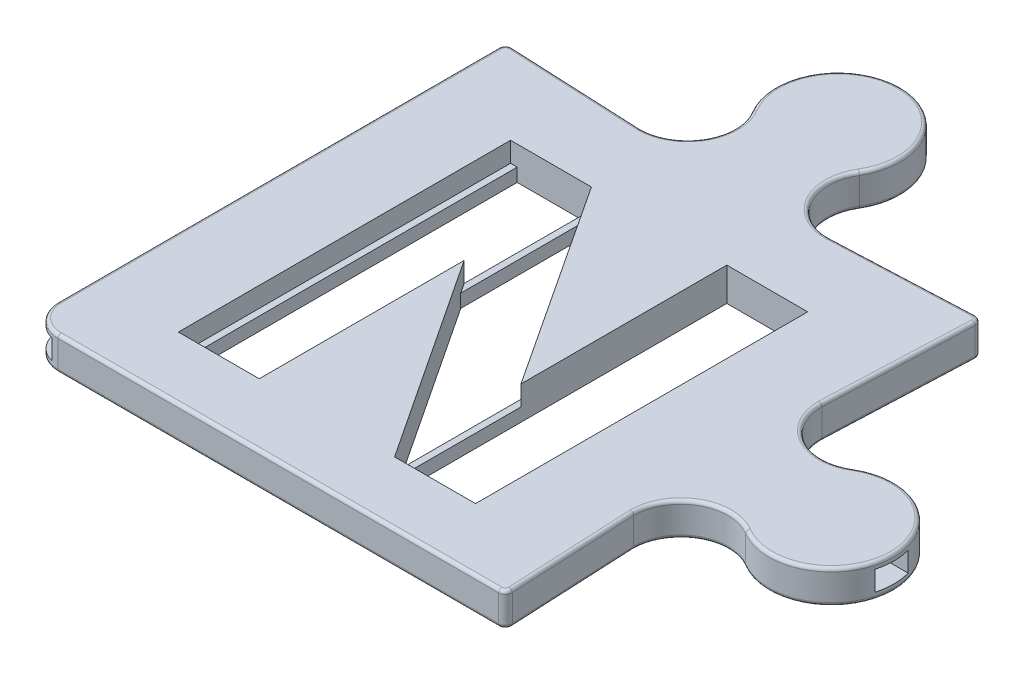
SolidWorks part; units mm, degrees
ref_plane "Front Plane" through (0, 0, 0) normal (0, 0, 1) x (1, 0, 0)
ref_plane "Top Plane" through (0, 0, 0) normal (0, 1, 0) x (1, 0, 0)
ref_plane "Right Plane" through (0, 0, 0) normal (1, 0, 0) x (0, 0, -1)
sketch "Sketch1" plane through (0, 0, 0) normal (0, 1, 0) x (1, 0, 0)
  line L0 (-31, -36) -> (37, -36) construction
  line L1 (-36, 37) -> (-36, -31) construction
  line L2 (-14.1421, 36) -> (-36, 37) construction
  line L3 (37, 37) -> (14.1421, 36) construction
  line L4 (36, 13.1421) -> (37, 37) construction
  line L5 (37, -36) -> (36, -15.1421) construction
  line L6 (-35.4, 36.3719) -> (-35.4, -31)
  line L7 (-36, 36) -> (36, 36) construction
  line L8 (-36, 36) -> (-36, -36) construction
  line L9 (-36, -36) -> (36, -36) construction
  line L10 (36, 36) -> (36, -36) construction
  line L11 (-31, -35.4) -> (36.3705, -35.4)
  line L12 (36.3705, -35.4) -> (35.4, -15.1568)
  line L13 (35.4, 13.155) -> (36.3732, 36.372)
  line L14 (36.3732, 36.372) -> (14.1555, 35.4)
  line L15 (-14.1562, 35.4) -> (-35.4, 36.3719)
  line L16 (-30, -24) -> (30, -24) construction
  line L17 (-30, 29) -> (30, 29) construction
  line L18 (-30, 29) -> (-30, -31) construction
  line L19 (-30, -31) -> (30, -31) construction
  line L20 (30, 29) -> (30, -31) construction
  line L21 (-30, 24) -> (30, 24) construction
  line L22 (-30, 24) -> (-30, -26) construction
  line L23 (-30, -26) -> (30, -26) construction
  line L24 (30, 24) -> (30, -26) construction
  arc A0 (-36, -31) -> (-31, -36) centre (-31, -31) ccw construction
  arc A1 (-14.1421, 36) -> (-8.571, 45.8485) centre (-14.1421, 42.5) ccw construction
  arc A2 (8.571, 45.8485) -> (-8.571, 45.8485) centre (0, 51) ccw construction
  arc A3 (8.571, 45.8485) -> (14.1421, 36) centre (14.1421, 42.5) ccw construction
  arc A4 (36, 13.1421) -> (45.8485, 7.571) centre (42.5, 13.1421) ccw construction
  arc A5 (45.8485, -9.571) -> (45.8485, 7.571) centre (51, -1) ccw construction
  arc A6 (45.8485, -9.571) -> (36, -15.1421) centre (42.5, -15.1421) ccw construction
  arc A7 (-35.4, -31) -> (-31, -35.4) centre (-31, -31) ccw
  arc A8 (46.1576, -9.0567) -> (35.4, -15.1568) centre (42.5, -15.1421) ccw
  arc A9 (46.1576, -9.0567) -> (46.1576, 7.0567) centre (51, -1) ccw
  arc A10 (35.4, 13.155) -> (46.1576, 7.0567) centre (42.5, 13.1421) ccw
  arc A11 (8.0567, 46.1576) -> (14.1555, 35.4) centre (14.1421, 42.5) ccw
  arc A12 (8.0567, 46.1576) -> (-8.0567, 46.1576) centre (0, 51) ccw
  arc A13 (-14.1562, 35.4) -> (-8.0567, 46.1576) centre (-14.1421, 42.5) ccw
  point P32 (36, 0)
  point P34 (0, 36)
  dimension "D5" = 6.5
  dimension "D6" = 10
  dimension "D7" = 6.5
  dimension "D13" = 5
  dimension "D9" = 10
  dimension "D11" = 6.5
  dimension "D12" = 6.5
  dimension "D1" = 72
  dimension "D2" = 1
  dimension "D3" = 1
  dimension "D4" = 15
  dimension "D8" = 1
  dimension "D10" = 35
  dimension "D14" = 15
  dimension "D15" = 36
  dimension "D16" = 1
  dimension "D18" = 60
  dimension "D19" = 60
  dimension "D20" = 5
  dimension "D21" = 6
  dimension "D22" = 5
  dimension "D23" = 50
  dimension "D24" = 2
  dimension "D17" = 0.6
extrude "Boss-Extrude1" add sketch "Sketch1" along normal blind 5
sketch "Sketch6" plane through (0, 0, 0) normal (0, -1, 0) x (1, 0, 0)
  line L0 (-35.4, -36.3719) -> (-35.4, 31) construction
  line L1 (-35.4, 18.4) -> (-27.4, 18.4)
  line L2 (-35.4, 18.4) -> (-35.4, -15.6)
  line L3 (-35.4, -15.6) -> (-27.4, -15.6)
  line L4 (-27.4, 18.4) -> (-27.4, -15.6)
  line L5 (-31, 35.4) -> (36.3705, 35.4) construction
  line L6 (-35.4, 15.15) -> (-30.4, 15.15)
  line L7 (-35.4, 15.15) -> (-35.4, -12.35)
  line L8 (-35.4, -12.35) -> (-30.4, -12.35)
  line L9 (-30.4, 15.15) -> (-30.4, -12.35)
  point P15 (-27.4, 1.4)
  point P16 (-30.4, 1.4)
  line M28 (-35.4, 31) -> (-35.4, -36.3719)
  dimension "D1" = 8
  dimension "D2" = 20.25
  dimension "D3" = 27.5
  dimension "D4" = 5
  dimension "D5" = 34
extrude "Cut-Extrude3" cut sketch "Sketch6" against normal blind 3 from offset 1 contours L6 L9 L8 L3 L4 L1 M28 | L9 L6 L2 L8 region at (-29.8665, 0, 1.4) region at (-32.9, 0, 1.4) offset against normal yes
extrude "Cut-Extrude4" cut sketch "Sketch6<3>" against normal up to next contours L9 L6 L2 L8 region at (-32.9, 0, 1.4)
sketch "Sketch6<3>" plane through (0, 0, 0) normal (0, -1, 0) x (1, 0, 0) same geometry as "Sketch6"
sketch "Sketch8" plane through (0, 0, 0) normal (0, -1, 0) x (1, 0, 0)
  line L1 (-2.5, -51.4) -> (2.5, -51.4)
  line L2 (-2.5, -51.4) -> (-2.5, -60.4)
  line L3 (-2.5, -60.4) -> (2.5, -60.4)
  line L4 (2.5, -51.4) -> (2.5, -60.4)
  line L5 (51.4, 3.5) -> (60.4, 3.5)
  line L6 (51.4, 3.5) -> (51.4, -1.5)
  line L7 (51.4, -1.5) -> (60.4, -1.5)
  line L8 (60.4, 3.5) -> (60.4, -1.5)
  arc A0 (-8.0567, -46.1576) -> (8.0567, -46.1576) centre (0, -51) ccw construction
  arc A1 (46.1576, -7.0567) -> (46.1576, 9.0567) centre (51, 1) ccw construction
  point P4 (0, -60.4)
  point P13 (60.4, 1)
  dimension "D1" = 5
  dimension "D2" = 9
  dimension "D3" = 5
  dimension "D4" = 9
extrude "Cut-Extrude5" cut sketch "Sketch8" against normal blind 3 from offset 1 offset against normal yes
sketch "Sketch9" plane through (0, 0, 0) normal (0, -1, 0) x (1, 0, 0)
  line L0 (-31, 35.4) -> (36.3705, 35.4) construction
  line L1 (-35.4, 15.15) -> (-35.4, 31) construction
  line L2 (-31.7636, 35.3332) -> (-35.4, 31) construction
  line L3 (-33.2571, 29.735) -> (-30.0429, 33.565) construction
  line L4 (-30.0429, 33.565) -> (-33.2571, 29.735) construction
  line L5 (-30.0429, 33.565) -> (-32.7119, 35.8048)
  line L6 (-33.2571, 29.735) -> (-35.926, 31.9747)
  line L7 (-32.7119, 35.8048) -> (-35.926, 31.9747)
  circle A0 centre (-31.65, 31.65) radius 2.5
  arc A1 (-31, 35.4) -> (-35.4, 31) centre (-31, 31) ccw construction
  arc M41 (-31, 35.4) -> (-35.4, 31) centre (-31, 31) ccw
  dimension "D1" = 5
  dimension "D3" = 3.75
  dimension "D4" = 5.6569
  dimension "D2" = 3.75
extrude "Cut-Extrude6" cut sketch "Sketch9" against normal blind 3 from offset 1 contours A0 L5 L6 M41 | A0 L5 region at (-33.6239, 0, 33.3064) region at (-31.65, 0, 31.65) offset against normal yes
sketch "Sketch11" plane through (-35.4, 0, 0) normal (-1, 0, 0) x (0, 0, 1)
  line L0 (-13.155, 0) -> (-36.372, 0) construction
  line L1 (-24.6, 3) -> (-18.6, 3)
  line L2 (-24.6, 3) -> (-24.6, 1.5)
  line L3 (-24.6, 1.5) -> (-18.6, 1.5)
  line L4 (-18.6, 3) -> (-18.6, 1.5)
  line L5 (-15.6, 4) -> (-15.6, 1) construction
  line L6 (35.4, 0) -> (15.1568, 0) construction
  line L7 (21.4, 3) -> (27.4, 3)
  line L8 (21.4, 3) -> (21.4, 1.5)
  line L9 (21.4, 1.5) -> (27.4, 1.5)
  line L10 (27.4, 3) -> (27.4, 1.5)
  line L12 (18.4, 4) -> (18.4, 1) construction
  dimension "D1" = 3
  dimension "D2" = 1.5
  dimension "D3" = 3
  dimension "D4" = 6
  dimension "D5" = 3
  dimension "D6" = 1.5
  dimension "D7" = 6
  dimension "D8" = 3
fillet "Fillet1" radius 0.5 17 edges at (-35.4, 0, 23.075) (-34.1113, 0, 34.1113) (2.6853, 0, 35.4) (35.8853, 0, 25.2784) (38.9978, 0, 8.966) (60.4, 0, 1) (38.9986, 0, -6.9655) (35.8866, 0, -24.7635) (25.2643, 0, -35.886) (7.9657, 0, -38.9984) (0, 0, -60.4) (-7.9658, 0, -38.9981) (-24.7781, 0, -35.886) (-35.4, 0, -24.361) (-32.9, 0, -12.35) (-30.4, 0, 1.4) (-32.9, 0, 15.15)
fillet "Fillet2" radius 0.5 13 edges at (-7.9658, 5, -38.9981) (0, 5, -60.4) (7.9657, 5, -38.9984) (25.2643, 5, -35.886) (35.8866, 5, -24.7635) (38.9986, 5, -6.9655) (60.4, 5, 1) (38.9978, 5, 8.966) (35.8853, 5, 25.2784) (2.6853, 5, 35.4) (-34.1113, 5, 34.1113) (-35.4, 5, -2.686) (-24.7781, 5, -35.886)
fillet "Fillet3" radius 1 9 edges at (36.2202, 0.1464, -36.2187) (36.2202, 4.8536, -36.2187) (36.3732, 2.5, -36.372) (-35.2536, 0.1464, -36.2186) (-35.2536, 4.8536, -36.2186) (36.2169, 0.1464, 35.2536) (36.2169, 4.8536, 35.2536) (36.3705, 2.5, 35.4) (-35.4, 2.5, -36.3719)
extrude "Cut-Extrude9" cut sketch "Sketch11" against normal blind 3
chamfer "Chamfer1" distance 1 angle 50 2 edges at (-35.4, 1.5, 24.4) (-35.4, 1.5, -21.6) first distance on face at (-35.4, 2.25, -21.6)
sketch "Sketch12" plane through (0, 5, 0) normal (0, 1, 0) x (1, 0, 0)
  text T0 "N" font "Poppins" height 50
extrude "Cut-Extrude10" cut sketch "Sketch12" against normal through all
sketch "Sketch13" plane through (0, 0, 0) normal (0, -1, 0) x (1, 0, 0)
  line L0 (-30, -24) -> (30, -24) construction
  line L1 (-22.2898, 26) -> (-21.2898, 26)
  line L2 (-22.2898, 26) -> (-22.2898, -24)
  line L3 (-22.2898, -24) -> (-21.2898, -24)
  line L4 (-21.2898, 26) -> (-21.2898, -24)
  line L5 (-10.1195, -24) -> (10.2535, 6.9769) construction
  line L6 (22.434, 26) -> (21.434, 26)
  line L7 (22.434, 26) -> (22.434, -24)
  line L8 (22.434, -24) -> (21.434, -24)
  line L9 (21.434, 26) -> (21.434, -24)
  line L10 (10.2535, 26) -> (-10.1195, -4.843) construction
  line L11 (9.2535, 5.4564) -> (10.2535, 5.4564)
  line L12 (9.2535, 5.4564) -> (9.2535, 26)
  line L13 (9.2535, 26) -> (10.2535, 26)
  line L14 (10.2535, 5.4564) -> (10.2535, 26)
  line L15 (-9.1195, -3.329) -> (-10.1195, -3.329)
  line L16 (-9.1195, -3.329) -> (-9.1195, -24)
  line L17 (-9.1195, -24) -> (-10.1195, -24)
  line L18 (-10.1195, -3.329) -> (-10.1195, -24)
  dimension "D1" = 1
  dimension "D2" = 1
  dimension "D3" = 1
  dimension "D4" = 1
extrude "Boss-Extrude2" add sketch "Sketch13" against normal blind 2
